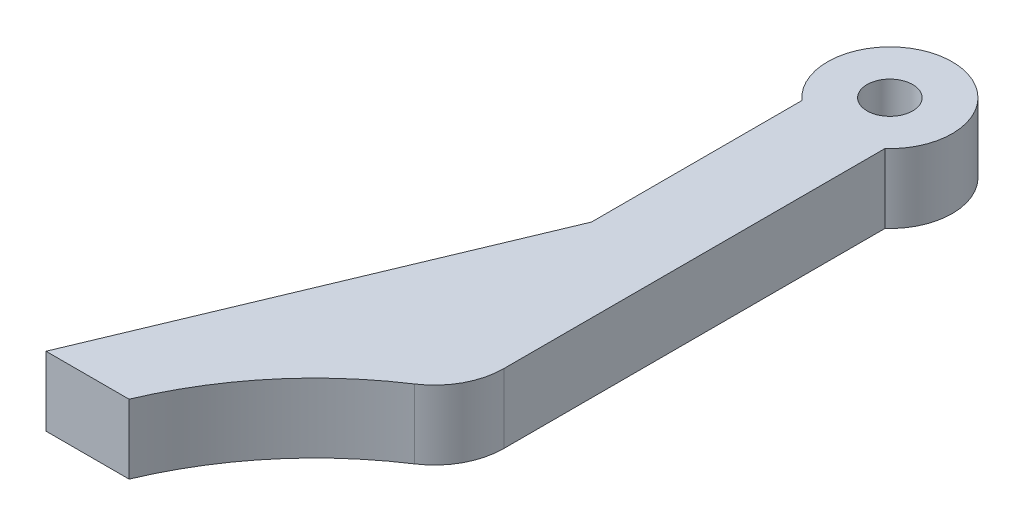
SolidWorks part; units mm, degrees
ref_plane "前视基准面" through (0, 0, 0) normal (0, 0, 1) x (1, 0, 0)
ref_plane "上视基准面" through (0, 0, 0) normal (0, 1, 0) x (1, 0, 0)
ref_plane "右视基准面" through (0, 0, 0) normal (1, 0, 0) x (0, 0, -1)
other "Configuration Table"
sketch "草图3" plane through (0, 0, 0) normal (0, 1, 0) x (1, 0, 0)
  line L0 (0, 0) -> (0, -9.9636) construction
  line L1 (-3, -3.3541) -> (3, -3.3541) construction
  line L2 (-3, -3.3541) -> (-3, -7.4162)
  line L3 (3, -3.3541) -> (3, -7.4162)
  line L7 (3, -7.4162) -> (3, -10.583)
  line L10 (-3, -43.8541) -> (3, -43.8541)
  line L11 (3, -43.8541) -> (3, -10.583)
  line L13 (-3, -7.4162) -> (-3, -43.8541)
  arc A0 (3, -3.3541) -> (-3, -3.3541) centre (0, 0) ccw
  point P6 (0, -3.3541)
  dimension "D1" = 9
  dimension "D2" = 6
  dimension "16.66" = 40.5
extrude "凸台-拉伸2" add sketch "草图3" along normal blind 5
sketch "草图4" plane through (0, 5, 0) normal (0, 1, 0) x (1, 0, 0)
  circle A0 centre (0, 0) radius 1.65
  dimension "D1" = 3.3
extrude "切除-拉伸1" cut sketch "草图4" against normal up to surface (5 mm away) up to face at (0, 0, 21.6406)
sketch "草图6" plane through (0, 5, 0) normal (0, 1, 0) x (1, 0, 0)
  line L0 (14.4495, -55.9701) -> (14.4495, -20.0301) construction
  line L1 (14.4495, -55.9701) -> (3, -43.8541) construction
  line L2 (3, -68.0861) -> (0.6636, -72.1328) construction
  line L3 (3, -43.8541) -> (-3, -43.8541) construction
  line L4 (3, -43.8541) -> (3, -33.746) construction
  line L5 (3, -43.8541) -> (3, -3.3541) construction
  line L6 (3, -33.746) -> (-3, -33.746)
  line L7 (-3, -3.3541) -> (-3, -43.8541) construction
  line L8 (14.4495, -55.9701) -> (1.9495, -77.6207) construction
  line L9 (1.9495, -77.6207) -> (0.7225, -79.746)
  arc A0 (3, -43.8541) -> (3, -68.0861) centre (14.4495, -55.9701) ccw construction
  arc A1 (-3, -43.8541) -> (0.6636, -72.1328) centre (14.4495, -55.9701) ccw construction
  arc A4 (3, -33.746) -> (1.9495, -77.6207) centre (14.4495, -55.9701) ccw
  arc A5 (-3, -33.746) -> (0.7225, -79.746) centre (8.4495, -55.9701) ccw
  dimension "D1" = 33.34
  dimension "D3" = 30
  dimension "D4" = 30
  dimension "D2" = 43.38
extrude "凸台-拉伸3" add sketch "草图6" against normal blind 5
sketch "草图7" plane through (0, 5, 0) normal (0, 1, 0) x (1, 0, 0)
  circle A0 centre (0, 0) radius 3
  dimension "D1" = 6
extrude "切除-拉伸2" cut sketch "草图7" against normal blind 3 from offset 4.5 offset against normal yes
sketch "草图8" plane through (0, 5, 0) normal (0, 1, 0) x (1, 0, 0)
  line L0 (-3, -38.0672) -> (-3, -43.8541)
  line L1 (-3, -43.8541) -> (3, -43.8541)
  line L2 (3, -43.8541) -> (3, -33.746)
  line L3 (3, -43.8541) -> (3, -3.3541) construction
  arc A0 (3, -33.746) -> (-3, -38.0672) centre (14.4495, -55.9701) ccw
extrude "切除-拉伸3" cut sketch "草图8" against normal blind 7.5
sketch "草图9" plane through (0, 5, 0) normal (0, 1, 0) x (1, 0, 0)
  line L0 (-3, -18.5501) -> (-14.615, -46.3249)
  line L1 (-3, -3.3541) -> (-3, -33.746) construction
  line L2 (-3, -18.5501) -> (-3, -33.746)
  arc A0 (-3, -33.746) -> (0.7225, -79.746) centre (8.4495, -55.9701) ccw construction
  arc A1 (-3, -33.746) -> (-14.615, -46.3249) centre (8.4495, -55.9701) ccw
extrude "凸台-拉伸4" add sketch "草图9" against normal blind 5
fillet "圆角1" radius 5 1 edges at (3, 2.5, 33.746)
fillet "圆角2" radius 5 1 edges at (1.9495, 2.5, 77.6207)
sketch "草图10" plane through (0, 5, 0) normal (0, 1, 0) x (1, 0, 0)
  line L0 (-14.615, -46.3249) -> (-8.615, -46.3249)
  line L3 (3, -30.882) -> (3, -3.3541)
  line L4 (-3, -3.3541) -> (-3, -18.5501)
  line L5 (-3, -18.5501) -> (-14.615, -46.3249)
  arc A5 (-14.615, -46.3249) -> (0.7225, -79.746) centre (8.4495, -55.9701) ccw
  arc A6 (0.7225, -79.746) -> (-1.1472, -75.5083) centre (-4.2666, -79.4159) ccw
  arc A7 (0.7416, -35.0633) -> (-1.1472, -75.5083) centre (14.4495, -55.9701) ccw
  arc A8 (0.7416, -35.0633) -> (3, -30.882) centre (-2, -30.882) ccw
  arc A9 (3, -3.3541) -> (-3, -3.3541) centre (0, 0) ccw
  arc A10 (-14.615, -46.3249) -> (0.7225, -79.746) centre (8.4495, -55.9701) ccw
  arc A11 (0.7225, -79.746) -> (-1.1472, -75.5083) centre (-4.2666, -79.4159) ccw
  arc A12 (-8.615, -46.3249) -> (-1.1472, -75.5083) centre (14.4495, -55.9701) ccw
  dimension "D1" = 0
extrude "切除-拉伸4" cut sketch "草图10" against normal blind 5
